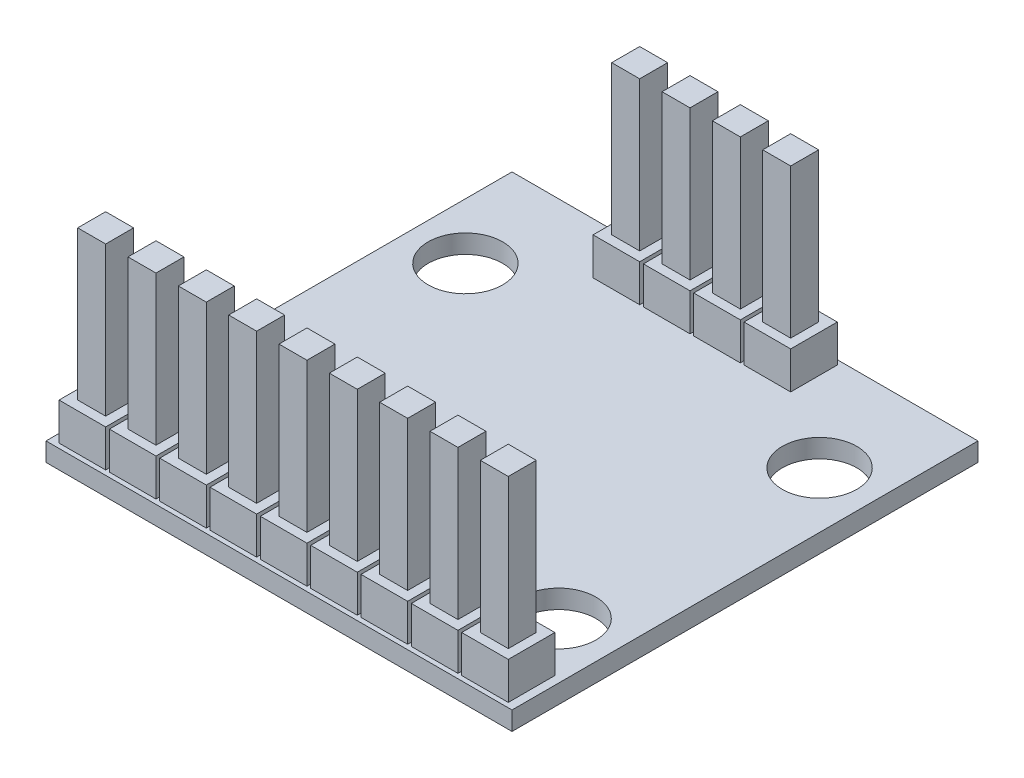
SolidWorks part; units mm, degrees
ref_plane "Спереди" through (0, 0, 0) normal (0, 0, 1) x (1, 0, 0)
ref_plane "Сверху" through (0, 0, 0) normal (0, 1, 0) x (1, 0, 0)
ref_plane "Справа" through (0, 0, 0) normal (1, 0, 0) x (0, 0, -1)
sketch "Эскиз1" plane through (0, 0, 0) normal (0, 1, 0) x (1, 0, 0)
  line L0 (1.45, -9.75) -> (3.95, -9.75)
  line L1 (12.5, -12.5) -> (-12.5, -12.5)
  line L2 (12.5, -12.5) -> (12.5, 12.5)
  line L3 (12.5, 12.5) -> (-12.5, 12.5)
  line L4 (-12.5, -12.5) -> (-12.5, 12.5)
  line L5 (12.5, -12.5) -> (-12.5, 12.5) construction
  line L6 (12.5, 12.5) -> (-12.5, -12.5) construction
  line L7 (9.5, -7) -> (-9.5, -7) construction
  line L8 (9.5, -7) -> (9.5, 7) construction
  line L9 (9.5, 7) -> (-9.5, 7) construction
  line L10 (-9.5, -7) -> (-9.5, 7) construction
  line L11 (9.5, -7) -> (-9.5, 7) construction
  line L12 (9.5, 7) -> (-9.5, -7) construction
  line L13 (-12.5, -11) -> (12.5, -11) construction
  line L15 (-1.25, -9.75) -> (1.25, -9.75)
  line L16 (-1.25, -9.75) -> (-1.25, -12.25)
  line L17 (-1.25, -12.25) -> (1.25, -12.25)
  line L18 (1.25, -9.75) -> (1.25, -12.25)
  line L19 (-1.25, -9.75) -> (1.25, -12.25) construction
  line L20 (-1.25, -12.25) -> (1.25, -9.75) construction
  line L36 (-1.25, -12.25) -> (1.35, -12.25) construction
  line L37 (-3.95, -12.25) -> (-1.45, -12.25)
  line L38 (-3.95, -9.75) -> (-1.45, -9.75)
  line L39 (-1.45, -9.75) -> (-1.45, -12.25)
  line L40 (-3.95, -9.75) -> (-3.95, -12.25)
  line L41 (-6.65, -12.25) -> (-4.15, -12.25)
  line L42 (-6.65, -9.75) -> (-4.15, -9.75)
  line L43 (-4.15, -9.75) -> (-4.15, -12.25)
  line L44 (-6.65, -9.75) -> (-6.65, -12.25)
  line L45 (-9.35, -12.25) -> (-6.85, -12.25)
  line L46 (-9.35, -9.75) -> (-6.85, -9.75)
  line L47 (-6.85, -9.75) -> (-6.85, -12.25)
  line L48 (-9.35, -9.75) -> (-9.35, -12.25)
  line L49 (-12.05, -12.25) -> (-9.55, -12.25)
  line L50 (-12.05, -9.75) -> (-9.55, -9.75)
  line L51 (-9.55, -9.75) -> (-9.55, -12.25)
  line L52 (-12.05, -9.75) -> (-12.05, -12.25)
  line L53 (-1.25, -12.25) -> (-3.95, -12.25) construction
  line L54 (1.45, -9.75) -> (1.45, -12.25)
  line L55 (-12.5, 11) -> (12.5, 11) construction
  line L56 (0, 12.25) -> (2.5, 12.25)
  line L57 (-2.7, 12.25) -> (-0.2, 12.25)
  line L58 (-2.7, 12.25) -> (-2.7, 9.75)
  line L59 (-2.7, 9.75) -> (-0.2, 9.75)
  line L60 (-0.2, 12.25) -> (-0.2, 9.75)
  line L61 (-2.7, 12.25) -> (-0.2, 9.75) construction
  line L62 (-2.7, 9.75) -> (-0.2, 12.25) construction
  line L63 (0, 12.25) -> (0, 9.75)
  line L64 (2.5, 12.25) -> (2.5, 9.75)
  line L65 (0, 9.75) -> (2.5, 9.75)
  line L66 (2.7, 12.25) -> (5.2, 12.25)
  line L67 (2.7, 12.25) -> (2.7, 9.75)
  line L68 (5.2, 12.25) -> (5.2, 9.75)
  line L69 (2.7, 9.75) -> (5.2, 9.75)
  line L70 (-2.7, 12.25) -> (0, 12.25) construction
  line L71 (-5.4, 9.75) -> (-2.9, 9.75)
  line L72 (-2.9, 12.25) -> (-2.9, 9.75)
  line L73 (-5.4, 12.25) -> (-2.9, 12.25)
  line L74 (-5.4, 12.25) -> (-5.4, 9.75)
  line L75 (-2.7, 9.75) -> (-5.4, 9.75) construction
  line L76 (1.45, -12.25) -> (3.95, -12.25)
  line L77 (3.95, -9.75) -> (3.95, -12.25)
  line L78 (1.45, -9.75) -> (3.95, -12.25) construction
  line L79 (1.45, -12.25) -> (3.95, -9.75) construction
  line L80 (1.45, -12.25) -> (4.05, -12.25) construction
  line L81 (4.15, -9.75) -> (6.65, -9.75)
  line L82 (4.15, -9.75) -> (4.15, -12.25)
  line L83 (4.15, -12.25) -> (6.65, -12.25)
  line L84 (6.65, -9.75) -> (6.65, -12.25)
  line L85 (4.15, -9.75) -> (6.65, -12.25) construction
  line L86 (4.15, -12.25) -> (6.65, -9.75) construction
  line L87 (4.15, -12.25) -> (6.75, -12.25) construction
  line L88 (6.85, -9.75) -> (9.35, -9.75)
  line L89 (6.85, -9.75) -> (6.85, -12.25)
  line L90 (6.85, -12.25) -> (9.35, -12.25)
  line L91 (9.35, -9.75) -> (9.35, -12.25)
  line L92 (6.85, -9.75) -> (9.35, -12.25) construction
  line L93 (6.85, -12.25) -> (9.35, -9.75) construction
  line L94 (6.85, -12.25) -> (9.45, -12.25) construction
  line L95 (9.55, -9.75) -> (12.05, -9.75)
  line L96 (9.55, -9.75) -> (9.55, -12.25)
  line L97 (9.55, -12.25) -> (12.05, -12.25)
  line L98 (12.05, -9.75) -> (12.05, -12.25)
  line L99 (9.55, -9.75) -> (12.05, -12.25) construction
  line L100 (9.55, -12.25) -> (12.05, -9.75) construction
  line L101 (9.55, -12.25) -> (12.15, -12.25) construction
  line L102 (0, -11) -> (2.7, -11) construction
  circle A0 centre (-9.5, 7) radius 2
  circle A1 centre (9.5, 7) radius 2
  circle A2 centre (9.5, -7) radius 2
  circle A3 centre (-9.5, -7) radius 2
  point P0 (0, 0)
  point P6 (0, 0)
  point P17 (0, -11)
  point P26 (2.7, -11)
  point P33 (5.4, -11)
  point P60 (-1.45, 11)
  point P66 (0, 11)
  point P67 (8.1, -11)
  point P89 (10.8, -11)
  dimension "D5" = 4
  dimension "D1" = 25
  dimension "D2" = 25
  dimension "D3" = 19
  dimension "D4" = 14
  dimension "D6" = 1.5
  dimension "D7" = 2.5
  dimension "D8" = 2.5
  dimension "D10" = 2.6
  dimension "D12" = 2.7
  dimension "D13" = 1.5
  dimension "D14" = 1.45
  dimension "D16" = 2.7
  dimension "D18" = 2.7
  dimension "D19" = 2.7
  dimension "D11" = 5
  dimension "D15" = 3
  dimension "D17" = 2
  dimension "D9" = 5
extrude "Бобышка-Вытянуть1" add sketch "Эскиз1" along normal blind 1
extrude "Бобышка-Вытянуть3" add sketch "Эскиз1<4>" along normal blind 3 contours L50 L52 L49 L51 | L46 L48 L45 L47 | L38 L40 L37 L39 | L18 L15 L16 L17 | L67 L69 L68 L66 | L63 L65 L64 L56 | L60 L57 L58 L59 | L73 L74 L71 L72 | L77 L0 L54 L76 | L84 L81 L82 L83 | L91 L88 L89 L90 | L98 L95 L96 L97 | L42 L43 L41 L44 region at (2.7, 0, 11) region at (0, 0, 11) region at (-2.7, 0, 11) region at (-8.1, 0, 11) region at (-10.8, 0, 11) region at (1.25, 0, -11) region at (-1.45, 0, -11) region at (3.95, 0, -11) region at (-4.15, 0, -11) region at (5.4, 0, 11) region at (8.1, 0, 11) region at (10.8, 0, 11)
sketch "Эскиз1<4>" plane through (0, 0, 0) normal (0, 1, 0) x (1, 0, 0) same geometry as "Эскиз1"
sketch "Эскиз3" plane through (0, 3, 0) normal (0, 1, 0) x (1, 0, 0)
  line L12 (-3.4, 11.75) -> (-4.9, 11.75)
  line L13 (-4.9, 11.75) -> (-4.9, 10.25)
  line L14 (-4.9, 10.25) -> (-3.4, 10.25)
  line L15 (-3.4, 10.25) -> (-3.4, 11.75)
  line L16 (-3.4, 11.75) -> (-4.9, 11.75)
  line L17 (-4.9, 11.75) -> (-4.9, 10.25)
  line L18 (-4.9, 10.25) -> (-3.4, 10.25)
  line L19 (-3.4, 10.25) -> (-3.4, 11.75)
  line L20 (-0.7, 11.75) -> (-2.2, 11.75)
  line L21 (-2.2, 11.75) -> (-2.2, 10.25)
  line L22 (-2.2, 10.25) -> (-0.7, 10.25)
  line L23 (-0.7, 10.25) -> (-0.7, 11.75)
  line L32 (2, 11.75) -> (0.5, 11.75)
  line L33 (0.5, 11.75) -> (0.5, 10.25)
  line L34 (0.5, 10.25) -> (2, 10.25)
  line L35 (2, 10.25) -> (2, 11.75)
  line L44 (4.7, 11.75) -> (3.2, 11.75)
  line L45 (3.2, 11.75) -> (3.2, 10.25)
  line L46 (3.2, 10.25) -> (4.7, 10.25)
  line L47 (4.7, 10.25) -> (4.7, 11.75)
  line L52 (-3.4, 11.75) -> (-0.7, 11.75) construction
  line L53 (-7.35, -10.25) -> (-8.85, -10.25)
  line L54 (-8.85, -10.25) -> (-8.85, -11.75)
  line L55 (-8.85, -11.75) -> (-7.35, -11.75)
  line L56 (-10.05, -10.25) -> (-11.55, -10.25)
  line L57 (-11.55, -10.25) -> (-11.55, -11.75)
  line L58 (-11.55, -11.75) -> (-10.05, -11.75)
  line L59 (-10.05, -11.75) -> (-10.05, -10.25)
  line L60 (-10.05, -10.25) -> (-11.55, -10.25)
  line L61 (-11.55, -10.25) -> (-11.55, -11.75)
  line L62 (-11.55, -11.75) -> (-10.05, -11.75)
  line L63 (-10.05, -11.75) -> (-10.05, -10.25)
  line L64 (-7.35, -11.75) -> (-7.35, -10.25)
  line L65 (-4.65, -10.25) -> (-6.15, -10.25)
  line L66 (-6.15, -10.25) -> (-6.15, -11.75)
  line L67 (-6.15, -11.75) -> (-4.65, -11.75)
  line L68 (-4.65, -11.75) -> (-4.65, -10.25)
  line L69 (-1.95, -10.25) -> (-3.45, -10.25)
  line L70 (-3.45, -10.25) -> (-3.45, -11.75)
  line L71 (-3.45, -11.75) -> (-1.95, -11.75)
  line L72 (-1.95, -11.75) -> (-1.95, -10.25)
  line L73 (0.75, -10.25) -> (-0.75, -10.25)
  line L74 (-0.75, -10.25) -> (-0.75, -11.75)
  line L75 (-0.75, -11.75) -> (0.75, -11.75)
  line L76 (0.75, -11.75) -> (0.75, -10.25)
  line L77 (3.45, -10.25) -> (1.95, -10.25)
  line L78 (1.95, -10.25) -> (1.95, -11.75)
  line L79 (1.95, -11.75) -> (3.45, -11.75)
  line L80 (3.45, -11.75) -> (3.45, -10.25)
  line L81 (6.15, -10.25) -> (4.65, -10.25)
  line L82 (4.65, -10.25) -> (4.65, -11.75)
  line L83 (4.65, -11.75) -> (6.15, -11.75)
  line L84 (6.15, -11.75) -> (6.15, -10.25)
  line L85 (8.85, -10.25) -> (7.35, -10.25)
  line L86 (7.35, -10.25) -> (7.35, -11.75)
  line L87 (7.35, -11.75) -> (8.85, -11.75)
  line L88 (8.85, -11.75) -> (8.85, -10.25)
  line L89 (11.55, -10.25) -> (10.05, -10.25)
  line L90 (10.05, -10.25) -> (10.05, -11.75)
  line L91 (10.05, -11.75) -> (11.55, -11.75)
  line L92 (11.55, -11.75) -> (11.55, -10.25)
  line L93 (-10.05, -10.25) -> (-7.35, -10.25) construction
  dimension "D3" = 2.7
  dimension "D6" = 2.7
  dimension "D1" = 0.5
  dimension "D2" = 4
  dimension "D4" = 9
  dimension "D5" = 0.5
extrude "Бобышка-Вытянуть4" add sketch "Эскиз3" along normal blind 8
